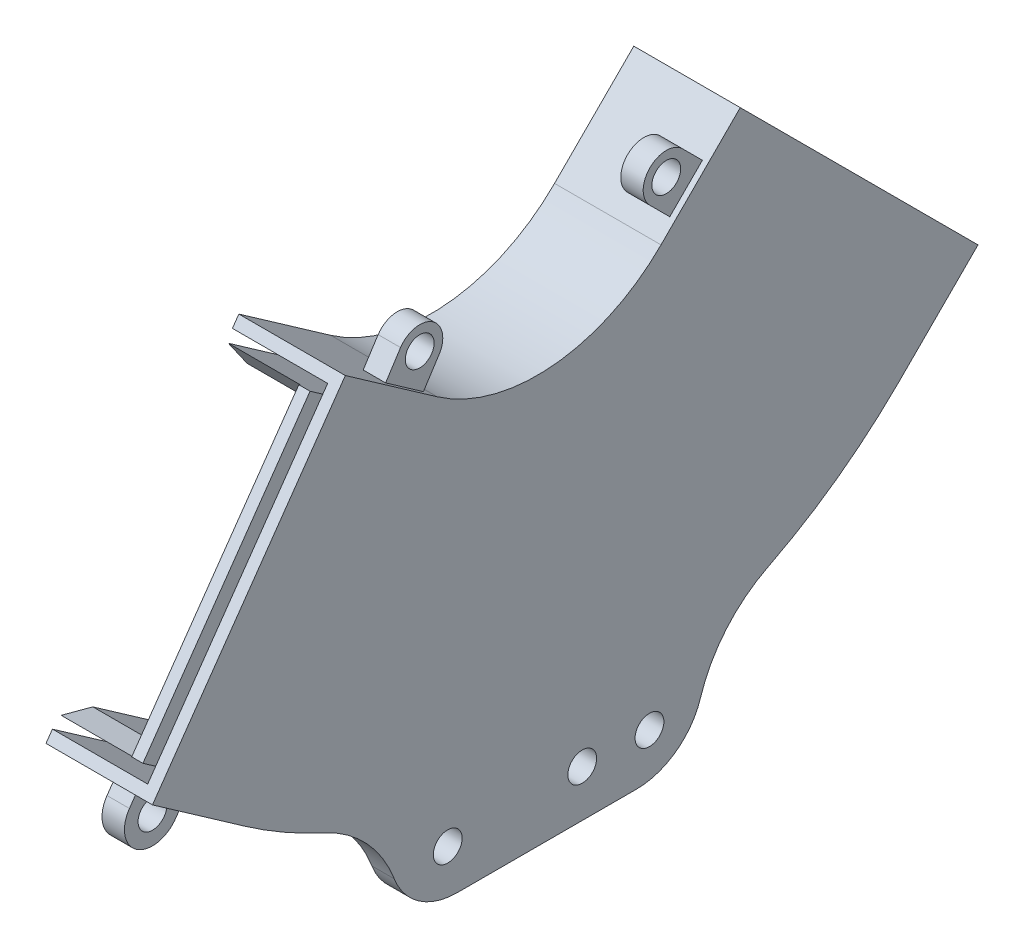
SolidWorks part; units mm, degrees
ref_plane "Front Plane" through (0, 0, 0) normal (0, 0, 1) x (1, 0, 0)
ref_plane "Top Plane" through (0, 0, 0) normal (0, 1, 0) x (1, 0, 0)
ref_plane "Right Plane" through (0, 0, 0) normal (1, 0, 0) x (0, 0, -1)
sketch "Sketch3" plane through (0, 0, 0) normal (1, 0, 0) x (0, 0, -1)
  line L0 (-22.7274, -32.4581) -> (-62.0633, -88.6355)
  line L1 (28.0184, -28.0184) -> (76.5118, -76.5118)
  line L2 (-22.7274, -32.4581) -> (0, 0) construction
  line L3 (0, 0) -> (28.0184, -28.0184) construction
  line L4 (0, 40.513) -> (0, -40.513) construction
  line L5 (-62.0633, -88.6355) -> (-66.4339, -94.8775)
  line L6 (76.5118, -76.5118) -> (81.8999, -81.8999)
  arc A2 (-62.0633, -88.6355) -> (76.5118, -76.5118) centre (0, 0) ccw
  arc A4 (-27.098, -38.7) -> (33.4066, -33.4066) centre (0, 0) ccw
  arc A5 (-22.7274, -32.4581) -> (28.0184, -28.0184) centre (0, 0) ccw
  arc A6 (-66.4339, -94.8775) -> (81.8999, -81.8999) centre (0, 0) ccw
  dimension "D1" = 216.408
  dimension "D2" = 135
  dimension "D3" = 94.488
  dimension "D4" = 7.62
  dimension "D6" = 7.62
  dimension "D5" = 80
extrude "Base extrude" add sketch "Sketch3" along normal blind 58.42 contours L5 A6 L6 A2 | A5 L0 A4 L1 region at (0, -39.9408, -3.4944) region at (0, -109.321, -9.5643)
sketch "Sketch4" plane through (58.42, 0, 0) normal (1, 0, 0) x (0, 0, -1)
  line L0 (-66.4339, -94.8775) -> (-22.7274, -32.4581)
  line L1 (28.0184, -28.0184) -> (81.8999, -81.8999)
  arc A0 (-22.7274, -32.4581) -> (28.0184, -28.0184) centre (0, 0) ccw
  arc A1 (-22.7274, -32.4581) -> (28.0184, -28.0184) centre (0, 0) ccw construction
  arc A2 (-66.4339, -94.8775) -> (81.8999, -81.8999) centre (0, 0) ccw
  arc A3 (-66.4339, -94.8775) -> (81.8999, -81.8999) centre (0, 0) ccw construction
  arc M1 (28.0184, -28.0184) -> (-22.7274, -32.4581) centre (0, 0) cw
  line M2 (-22.7274, -32.4581) -> (-27.098, -38.7)
  arc M3 (-27.098, -38.7) -> (33.4066, -33.4066) centre (0, 0) ccw
  line M4 (33.4066, -33.4066) -> (28.0184, -28.0184)
extrude "Outer wall" add sketch "Sketch4" along normal blind 7.62 contours L0 A2 L1 M3 | M4 M1 M2 M3 region at (58.42, -79.1939, -6.9286) region at (58.42, -39.9408, -3.4944)
ref_plane "Midplane" through (29.21, 0, 0) normal (-1, 0, 0) x (0, 0, 1)
mirror "Mirror1" about plane through (29.21, 0, 0) normal (-1, 0, 0) of "Outer wall"
sketch "Sketch6" plane through (0, 0, 0) normal (0, 0.5736, 0.8192) x (1, 0, 0)
  line L27 (-5.08, -42.164) -> (63.5, -42.164)
  line L28 (-5.08, -42.164) -> (-5.08, -113.284)
  line L29 (-5.08, -113.284) -> (63.5, -113.284)
  line L30 (63.5, -42.164) -> (63.5, -113.284)
  line L31 (-2.54, -44.704) -> (60.96, -44.704)
  line L32 (-2.54, -44.704) -> (-2.54, -110.744)
  line L33 (-2.54, -110.744) -> (60.96, -110.744)
  line L34 (60.96, -44.704) -> (60.96, -110.744)
  line L35 (58.42, -47.244) -> (0, -47.244) construction
  line L36 (0, -108.204) -> (0, -18.7894) construction
  line L37 (58.42, -18.7894) -> (58.42, -108.204) construction
  line L38 (58.42, -108.204) -> (0, -108.204) construction
  line L40 (0, -47.244) -> (58.42, -47.244)
  line L41 (0, -47.244) -> (0, -108.204)
  line L42 (0, -108.204) -> (58.42, -108.204)
  line L43 (58.42, -47.244) -> (58.42, -108.204)
  line L44 (-7.62, -39.624) -> (66.04, -39.624)
  line L45 (-7.62, -39.624) -> (-7.62, -115.824)
  line L46 (-7.62, -115.824) -> (66.04, -115.824)
  line L47 (66.04, -39.624) -> (66.04, -115.824)
  line M21 (-7.62, -39.624) -> (-7.62, -115.824)
  line M22 (-7.62, -115.824) -> (66.04, -115.824)
  line M23 (66.04, -115.824) -> (66.04, -39.624)
  line M24 (66.04, -39.624) -> (-7.62, -39.624)
  line M25 (58.42, -108.204) -> (0, -108.204)
  line M26 (0, -108.204) -> (0, -47.244)
  line M27 (0, -47.244) -> (58.42, -47.244)
  line M28 (58.42, -47.244) -> (58.42, -108.204)
  dimension "D1" = 2.54
  dimension "D2" = 2.54
  dimension "D3" = 2.54
  dimension "D4" = 2.54
  dimension "D5" = 2.54
  dimension "D6" = 2.54
  dimension "D7" = 2.54
  dimension "D8" = 2.54
extrude "Endcap 1" add sketch "Sketch6" along normal blind 25.4 contours L27 L30 L29 L28 M24 M21 M22 M23 | L34 L31 L32 L33 M28 M25 M26 M27 region at (29.21, -37.3698, 26.1667) region at (29.21, -33.3262, 23.3353)
sketch "Sketch7" plane through (0, 0, 0) normal (0, 0.7071, -0.7071) x (1, 0, 0)
  line L0 (-5.08, 113.284) -> (63.5, 113.284)
  line L1 (-5.08, 113.284) -> (-5.08, 42.164)
  line L2 (-5.08, 42.164) -> (63.5, 42.164)
  line L3 (63.5, 113.284) -> (63.5, 42.164)
  line L4 (-2.54, 110.744) -> (60.96, 110.744)
  line L5 (-2.54, 110.744) -> (-2.54, 44.704)
  line L6 (-2.54, 44.704) -> (60.96, 44.704)
  line L7 (60.96, 110.744) -> (60.96, 44.704)
  line L8 (0, 108.204) -> (58.42, 108.204)
  line L9 (0, 108.204) -> (0, 47.244)
  line L10 (0, 47.244) -> (58.42, 47.244)
  line L11 (58.42, 108.204) -> (58.42, 47.244)
  line L12 (-7.62, 115.824) -> (66.04, 115.824)
  line L13 (-7.62, 115.824) -> (-7.62, 39.624)
  line L14 (-7.62, 39.624) -> (66.04, 39.624)
  line L15 (66.04, 115.824) -> (66.04, 39.624)
  line L16 (58.42, 108.204) -> (0, 108.204) construction
  line L17 (58.42, 47.244) -> (58.42, 108.204) construction
  line L18 (66.04, 115.824) -> (-7.62, 115.824) construction
  line L19 (66.04, 39.624) -> (66.04, 115.824) construction
  line L20 (-7.62, 39.624) -> (-7.62, 115.824) construction
  line L21 (66.04, 39.624) -> (-7.62, 39.624) construction
  line M17 (66.04, 115.824) -> (-7.62, 115.824)
  line M18 (-7.62, 115.824) -> (-7.62, 39.624)
  line M19 (-7.62, 39.624) -> (66.04, 39.624)
  line M20 (66.04, 39.624) -> (66.04, 115.824)
  line M21 (0, 47.244) -> (0, 108.204)
  line M22 (0, 108.204) -> (58.42, 108.204)
  line M23 (58.42, 108.204) -> (58.42, 47.244)
  line M24 (58.42, 47.244) -> (0, 47.244)
  dimension "D1" = 2.54
  dimension "D2" = 2.54
  dimension "D3" = 2.54
  dimension "D4" = 2.54
  dimension "D5" = 2.54
  dimension "D6" = 2.54
  dimension "D7" = 2.54
  dimension "D8" = 2.54
extrude "Endcap 2" add sketch "Sketch7" along normal blind 25.4 contours L0 L3 L2 L1 M20 M17 M18 M19 | L7 L4 L5 L6 M24 M21 M22 M23 region at (29.21, -77.66, -77.66) region at (29.21, -81.1505, -81.1505)
chamfer "Internal Chamfer" distance 7.62 angle 20 4 edges at (29.21, -74.0667, 82.8697) (29.21, -24.1312, 47.9045) (29.21, -58.5513, -94.4723) (29.21, -15.446, -51.3671) first distance on face at (29.21, -81.3511, 72.4665) first distance on face at (29.21, -31.4156, 37.5013) first distance on face at (29.21, -67.5315, -85.492) first distance on face at (29.21, -24.4263, -42.3868)
ref_plane "Plane2" through (0, -13.9736, -1.2225) normal (0, -0.9962, -0.0872) x (-1, 0, 0)
sketch "Sketch10" plane through (0, -13.9736, -1.2225) normal (0, -0.9962, -0.0872) x (-1, 0, 0)
  line L0 (-66.04, 93.9078) -> (7.62, 93.9078) construction
  line L1 (-16.51, 95.5358) -> (-41.91, 95.5358)
  line L2 (-16.51, 95.5358) -> (-16.51, -82.1857)
  line L3 (-16.51, -82.1857) -> (-41.91, -82.1857)
  line L4 (-41.91, 95.5358) -> (-41.91, -82.1857)
  point P4 (-29.21, 93.9078)
  point P5 (-29.21, 95.5358)
  dimension "D1" = 25.4
extrude "Flywheel Hole" cut sketch "Sketch10" along normal up to next
sketch "Sketch11" plane through (-7.62, 0, 0) normal (-1, 0, 0) x (0, 0, 1)
  line L0 (-25.2982, 2.2719) -> (-28.0184, -28.0184)
  line L4 (-3.0636, -22.3183) -> (-4.5937, -39.3568)
  line L5 (6.8995, -21.445) -> (11.3704, -37.9575)
  line L6 (-20.4217, -1.79) -> (20.4217, 1.79) construction
  line L7 (24.5172, 6.6383) -> (33.1306, -25.1737)
  line L8 (43.5339, -17.8892) -> (22.7274, -32.4581) construction
  line L10 (1.5525, -17.7121) -> (-2.2178, 25.303) construction
  line L11 (22.7274, -32.4581) -> (43.5339, -17.8892)
  line L12 (22.7274, -32.4581) -> (33.1306, -25.1737)
  arc A1 (-28.0184, -28.0184) -> (22.7274, -32.4581) centre (0, 0) ccw construction
  circle A3 centre (0, 0) radius 4.064
  arc A4 (24.5172, 6.6383) -> (-25.2982, 2.2719) centre (0, 0) ccw
  circle A6 centre (-20.4217, -1.79) radius 2.5
  circle A7 centre (20.4217, 1.79) radius 2.5
  arc A8 (-3.0636, -22.3183) -> (6.8995, -21.445) centre (1.9961, -22.7727) cw
  arc A11 (11.3704, -37.9575) -> (22.7274, -32.4581) centre (0, 0) ccw
  arc A12 (-28.0184, -28.0184) -> (22.7274, -32.4581) centre (0, 0) ccw
  arc A13 (-28.0184, -28.0184) -> (-4.5937, -39.3568) centre (0, 0) ccw
  point P22 (0, 0)
  dimension "D3" = 8.128
  dimension "D2" = 25.4
  dimension "D1" = 5
  dimension "D5" = 5.08
  dimension "D4" = 41
  dimension "D7" = 43.18
  dimension "D6" = 0
extrude "Flywheel holder" add sketch "Sketch11" against normal blind 7.62
sketch "Sketch12" plane through (-7.62, 0, 0) normal (-1, 0, 0) x (0, 0, 1)
  circle A0 centre (0, 0) radius 14.605
  dimension "D1" = 29.21
extrude "Motor insert" cut sketch "Sketch12" against normal blind 6.35
sketch "Sketch14" plane through (-7.62, 0, 0) normal (-1, 0, 0) x (0, 0, 1)
  line L1 (-106.5763, 40.9543) -> (105.556, 40.9543)
  line L2 (-106.5763, 40.9543) -> (-106.5763, -120.0185)
  line L3 (-106.5763, -120.0185) -> (105.556, -120.0185)
  line L4 (105.556, 40.9543) -> (105.556, -120.0185)
extrude "Cut-Extrude2" cut sketch "Sketch14" against normal up to surface (49.53 mm away) up to face at (41.91, -26.9401, -2.3569)
sketch "Sketch15" plane through (41.91, 0, 0) normal (-1, 0, 0) x (0, 0, 1)
  line L0 (-93.8083, -77.7308) -> (-89.6212, -74.1787)
  line L1 (-99.8604, -63.9394) -> (-81.8999, -81.8999) construction
  line L2 (-89.6212, -74.1787) -> (-80.6312, -83.1493)
  line L3 (-80.6312, -83.1493) -> (-85.0539, -86.9012)
  line L4 (-16.51, -121.4959) -> (-16.51, -114.6413)
  line L5 (-16.51, -114.6413) -> (-3.8593, -115.7597)
  line L6 (-3.8593, -115.7597) -> (-3.8593, -120.7059)
  line L7 (63.1155, -104.8839) -> (59.3284, -99.4753)
  line L8 (59.3284, -99.4753) -> (69.9059, -92.4464)
  line L9 (66.4339, -94.8775) -> (87.2404, -80.3086) construction
  line L10 (69.9059, -92.4464) -> (73.4123, -97.454)
  circle A0 centre (-89.7004, -82.5731) radius 3.2639
  circle A1 centre (-10.16, -121.4959) radius 3.2639
  circle A2 centre (68.1904, -101.0671) radius 3.2639
  arc A3 (-93.8083, -77.7308) -> (-85.0539, -86.9012) centre (-89.7004, -82.5731) ccw
  arc A5 (62.868, -104.5305) -> (73.3715, -97.3959) centre (68.1904, -101.0671) ccw
  arc A6 (-81.8999, -81.8999) -> (66.4339, -94.8775) centre (0, 0) ccw construction
  arc A7 (-16.51, -121.4959) -> (-3.8593, -120.7059) centre (-10.16, -121.4959) ccw
  line M28 (-99.8604, -63.9394) -> (-81.8999, -81.8999)
  arc M29 (-81.8999, -81.8999) -> (66.4339, -94.8775) centre (0, 0) ccw
  line M30 (66.4339, -94.8775) -> (87.2404, -80.3086)
  dimension "D4" = 6.5278
  dimension "D5" = 12.7
  dimension "D1" = 121.92
  dimension "D2" = 121.92
  dimension "D3" = 121.92
  dimension "D6" = 10.16
  dimension "D7" = 10.16
  dimension "D8" = 19.05
  dimension "D9" = 12.7
  dimension "D10" = 12.7
  dimension "D11" = 12.7
extrude "Joining screw holes" add sketch "Sketch15" against normal blind 5.08 contours L0 A3 L3 A0 M29 M28 | L4 A7 L6 A1 M29 | L7 A5 L10 A2 M30 M29 region at (41.91, -97.4205, 63.0391) region at (41.91, -115.5565, -10.2161) region at (41.91, -76.1174, -91.5767)
ref_plane "Plane3" through (59.69, 0, 0) normal (1, 0, 0) x (0, 0, -1)
sketch "Sketch16" plane through (59.69, 0, 0) normal (1, 0, 0) x (0, 0, -1)
  line L0 (-43.5339, -17.8892) -> (-22.7274, -32.4581) construction
  line L1 (45.9789, -10.0579) -> (28.0184, -28.0184) construction
  line L2 (-29.7459, -19.9251) -> (-33.1306, -25.1737)
  line L3 (-33.1306, -25.1737) -> (-24.5641, -31.172)
  line L4 (-24.5641, -31.172) -> (-21.1794, -25.9235)
  line L5 (26.7818, -20.2747) -> (31.2719, -24.7649)
  line L6 (31.2719, -24.7649) -> (38.6683, -17.3685)
  line L7 (38.6683, -17.3685) -> (34.1782, -12.8783)
  line L8 (34.1782, -12.8783) -> (26.7818, -20.2747) construction
  circle A0 centre (-25.4, -22.8348) radius 3.2639
  circle A1 centre (30.48, -16.5765) radius 3.2639
  arc A2 (-21.1794, -25.9235) -> (-29.8435, -20.0764) centre (-25.4, -22.8348) ccw
  arc A3 (34.1782, -12.8783) -> (26.7818, -20.2747) centre (30.48, -16.5765) ccw
  dimension "D3" = 6.5278
  dimension "D1" = 6.35
  dimension "D2" = 6.35
  dimension "D4" = 25.4
  dimension "D5" = 30.48
  dimension "D6" = 55.88
  dimension "D7" = 6.2582
extrude "Flywheel cover connectors" add sketch "Sketch16" along normal blind 5.08 contours L4 A2 L2 L3 A0 | L7 L8 A1 L5 L6 | L8 A3 A1 region at (59.69, -18.7043, 22.5078) region at (59.69, -19.2478, -33.1513) region at (59.69, -12.9676, -26.8711)
sketch "Sketch17" plane through (66.04, 0, 0) normal (1, 0, 0) x (0, 0, -1)
  line L0 (-30.48, -111.7415) -> (-30.48, -132.08)
  line L1 (-30.48, -132.08) -> (35.56, -132.08)
  line L2 (35.56, -132.08) -> (35.56, -110.2301)
  circle A0 centre (-20.32, -121.92) radius 3.2639
  circle A1 centre (25.4, -121.92) radius 3.2639
  arc A2 (-66.4339, -94.8775) -> (81.8999, -81.8999) centre (0, 0) ccw construction
  circle A4 centre (10.16, -121.4959) radius 3.2639
  arc A5 (-66.4339, -94.8775) -> (81.8999, -81.8999) centre (0, 0) ccw
  arc A6 (-30.48, -111.7415) -> (35.56, -110.2301) centre (0, 0) ccw
  circle A7 centre (10.16, -121.4959) radius 3.2639 construction
  dimension "D1" = 6.5278
  dimension "D2" = 20.32
  dimension "D3" = 25.4
  dimension "D4" = 121.92
  dimension "D5" = 0
  dimension "D6" = 10.16
  dimension "D7" = 10.16
  dimension "D8" = 10.16
extrude "80-20 connector" add sketch "Sketch17" against normal blind 5.08
fillet "Fillet1" radius 30.48 2 edges at (63.5, -111.7415, 30.48) (63.5, -110.2301, -35.56)
fillet "Fillet2" radius 15.24 2 edges at (63.5, -132.08, -35.56) (63.5, -132.08, 30.48)
